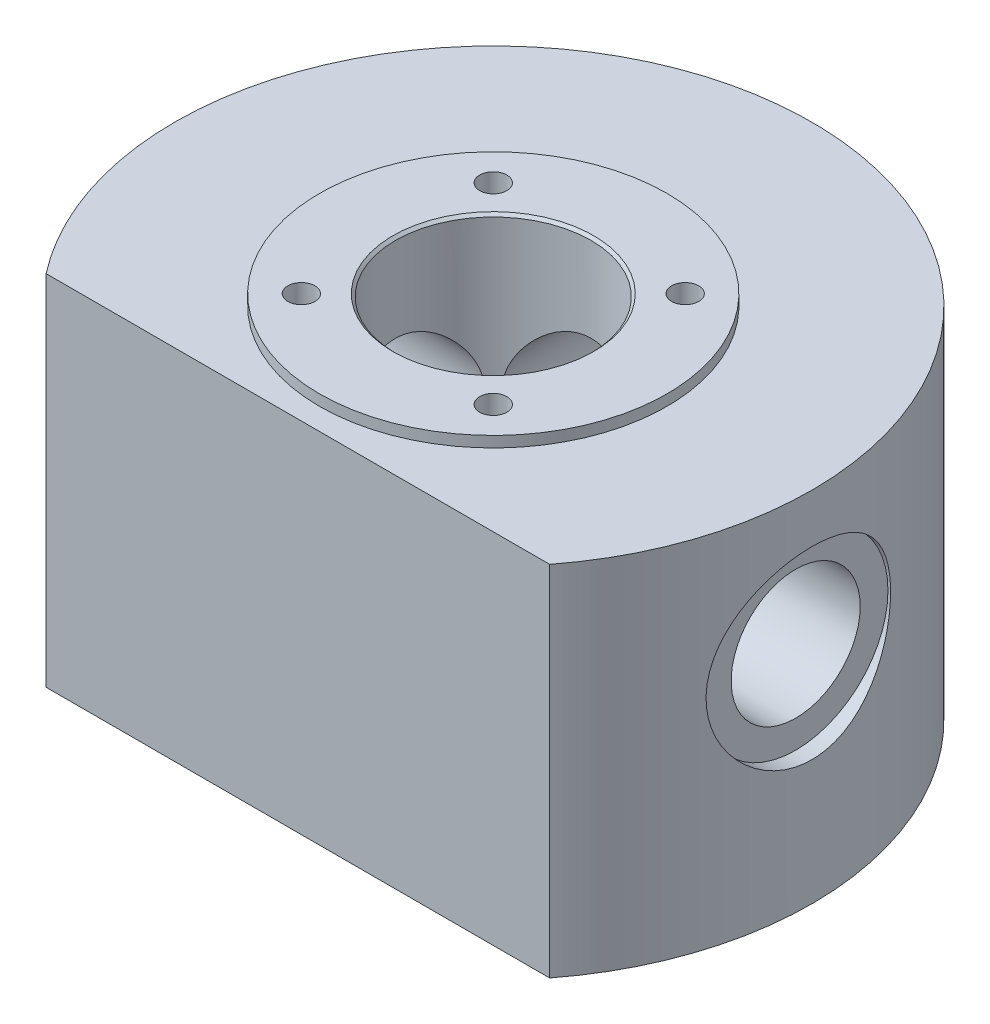
SolidWorks part; units mm, degrees
material "Chrome Stainless Steel"
ref_plane "Plano frontal" through (0, 0, 0) normal (0, 0, 1) x (1, 0, 0)
ref_plane "Plano superior" through (0, 0, 0) normal (0, 1, 0) x (1, 0, 0)
ref_plane "Plano direito" through (0, 0, 0) normal (1, 0, 0) x (0, 0, -1)
sketch "Esboço1" plane through (0, 0, 0) normal (0, 0, 1) x (1, 0, 0)
  line L0 (0, -20) -> (0, 0) construction
  line L1 (0, 0) -> (9, 0) construction
  line L2 (0, -20) -> (29.356, -20)
  line L3 (29.356, 13) -> (29.356, -20)
  line L4 (29.356, 13) -> (9, 13)
  line L5 (9, 13) -> (9, -13)
  line L6 (9, -13) -> (3, -13)
  line L7 (3, -13) -> (3, -17.6)
  line L8 (0, -20) -> (43.826, -20) construction
  line L9 (3, -17.6) -> (0, -17.6)
  line L10 (0, -17.6) -> (0, -20)
  dimension "D1" = 7
  dimension "D2" = 18
  dimension "D3" = 6
  dimension "D4" = 33
  dimension "D5" = 58.712
  dimension "D6" = 4.6
revolve "Revolução1" add sketch "Esboço1" angle 360 about L0
hole_wizard "Furo roscado de 1/4-18 NPSM1" positions "3DSketch2" profile "Esboço4" tap size "1/4-18 NPSM" standard "Ansi Inch" end condition up to next
sketch3d "3DSketch2"
  point P0 (0, 0, 0)
  point P4 (0, 0, 0)
  point P6 (29.356, 0, 0)
sketch "Esboço4" plane through (29.356, 0, 0) normal (0, 1, 0) x (0, 0, -1)
  line L0 (0, 0) -> (0, 29.356)
  line L1 (0, 29.356) -> (5.9436, 29.356)
  line L2 (5.9436, 29.356) -> (5.9436, 0)
  line L5 (5.9436, 0) -> (0, 0)
  line L11 (0, -6.35) -> (0, 107.95) construction
  dimension "Thru Tap Drill Dia." = 11.8872
  dimension "Thru Tap Drill Depth" = 29.356
cosmetic thread "Rosca de furo1" parameters "D2"=13.3604
ref_plane "Plano1" through (0, 0, -29.356) normal (0, 0, 1) x (0, -1, 0)
hole_wizard "Furo roscado de 1/4-18 NPSM3" positions "Esboço6" profile "Esboço5" tap size "1/4-18 NPSM" standard "Ansi Inch" end condition up to next
sketch "Esboço6" plane through (0, 0, -29.356) normal (0, 0, 1) x (0, -1, 0)
  point P0 (0, 0)
sketch "Esboço5" plane through (0, 0, -29.356) normal (1, 0, 0) x (0, 1, 0)
  line L0 (0, 0) -> (0, 20.356)
  line L1 (0, 20.356) -> (5.9436, 20.356)
  line L2 (5.9436, 20.356) -> (5.9436, 0)
  line L5 (5.9436, 0) -> (0, 0)
  line L11 (0, -6.35) -> (0, 107.95) construction
  dimension "Thread Major Dia." = 11.8872
  dimension "Thru Tap Drill Depth" = 20.356
ref_plane "Plano2" through (-29.356, 0, 0) normal (-1, 0, 0) x (0, -1, 0)
sketch "Esboço7" plane through (-29.356, 0, 0) normal (-1, 0, 0) x (0, -1, 0)
  circle A0 centre (0, 0) radius 3
  dimension "D1" = 6
extrude "Corte-extrusão1" [suppressed] cut sketch "Esboço7" against normal blind 6
ref_axis "Eixo1" through (0, 15.7, 0) along (0, -1, 0)
pattern_circular "PadrãoCircular1" [suppressed] count 2 every 17 about axis through (0, 15.7, 0) along (0, -1, 0) of bodies 131
pattern_circular "PadrãoCircular2" [suppressed] count 2 over 360 about axis through (0, 15.7, 0) along (0, -1, 0) of bodies 132
sketch "Esboço8" [suppressed] plane through (-16, 0, 0) normal (-1, 0, 0) x (0, -1, 0)
  line L0 (9.5, -16) -> (9.5, 16) construction
  line L1 (-6, -4) -> (9.5, -4)
  line L2 (-6, -4) -> (-6, 4)
  line L3 (-6, 4) -> (9.5, 4)
  line L4 (9.5, -4) -> (9.5, 4)
  circle A1 centre (0, 0) radius 3 construction
  dimension "D2" = 4
  dimension "D3" = 4
  dimension "D1" = 6
extrude "Corte-extrusão2" [suppressed] cut sketch "Esboço8" against normal blind 2
pattern_circular "PadrãoCircular3" [suppressed] count 2 every 17 about axis through (0, 15.7, 0) along (0, -1, 0) of bodies 134
pattern_circular "PadrãoCircular4" [suppressed] count 2 over 360 about axis through (0, 15.7, 0) along (0, -1, 0) of bodies 135
ref_plane "Plano3" through (0, -20, 0) normal (0, -1, 0) x (-1, 0, 0)
sketch "Esboço9" [suppressed] plane through (0, -9.5, 0) normal (0, -1, 0) x (-1, 0, 0)
  line L0 (14, -7.746) -> (14, 2.0923)
  line L1 (14, 2.0923) -> (11.1236, 11.5007)
  line L2 (12.2188, 7.9184) -> (14, 2.0923) construction
  line L3 (14, -4) -> (14, 2.0923) construction
  line L6 (-14, -7.746) -> (-14, 7.746)
  line L8 (-14, 4) -> (-14, -4) construction
  arc A0 (14, -7.746) -> (11.1236, 11.5007) centre (0, 0) ccw
  arc A1 (-14, 7.746) -> (-14, -7.746) centre (0, 0) ccw
extrude "Corte-extrusão3" [suppressed] cut sketch "Esboço9" against normal through all
ref_plane "Plano4" through (0, 13, 0) normal (0, 1, 0) x (1, 0, 0)
sketch "Esboço12" plane through (0, 13, 0) normal (0, 1, 0) x (1, 0, 0)
  circle A0 centre (0, 0) radius 9
  circle A1 centre (0, 0) radius 16
  dimension "D1" = 18
  dimension "D2" = 32
extrude "Ressalto-extrusão1" add sketch "Esboço12" along normal blind 1
hole_wizard "Furo roscado de M3x0.51" positions "Esboço14" profile "Esboço13" tap size "M3x0.5" standard "Ansi Metric"
sketch "Esboço14" plane through (0, 14, 0) normal (0, 1, 0) x (1, 0, 0)
  line L0 (0, 16) -> (0, 0) construction
  line L1 (0, 0) -> (11.3137, 11.3137) construction
  circle A0 centre (0, 0) radius 12.5
  circle A1 centre (0, 0) radius 16 construction
  point P0 (8.8388, 8.8388)
  dimension "D2" = 25
  dimension "D1" = 45
sketch "Esboço13" plane through (8.8388, 14, -8.8388) normal (1, 0, 0) x (0, 0, 1)
  line L0 (0, 0) -> (0, 10.7511)
  line L1 (0, 10.7511) -> (1.25, 10)
  line L2 (1.25, 10) -> (1.25, 0)
  line L5 (1.25, 0) -> (0, 0)
  line L10 (0, 10.7511) -> (-1.25, 10) construction
  line L11 (0, -6.35) -> (0, 107.95) construction
  dimension "Tap Drill Dia." = 2.5
  dimension "Tap Drill Depth" = 10
  dimension "Drill Angle" = 118
ref_axis "Eixo2" through (0, -21.7, 0) along (0, 1, 0)
pattern_circular "PadrãoCircular5" count 4 over 360 about axis through (0, -21.7, 0) along (0, 1, 0) of "Furo roscado de M3x0.51"
chamfer "Chanfro1" distance 0.5 angle 45 1 edges at (0, -13, -3)
chamfer "Chanfro2" distance 0.25 angle 45 1 edges at (0, 14, 9)
hole_wizard "Furo roscado de 1/4-18 NPSM2" positions "3DSketch4" profile "Esboço17" tap size "1/4-18 NPSM" standard "Ansi Inch" end condition up to next
sketch3d "3DSketch4"
  line L0 (0, 0, 0) -> (0, 0, 1.819) construction
  line L4 (0, 0, 0) -> (-29.356, 0, 0)
  point P0 (-29.356, 0, 0)
sketch "Esboço17" plane through (-29.356, 0, 0) normal (0, 1, 0) x (0, 0, 1)
  line L0 (0, 0) -> (0, 20.356)
  line L1 (0, 20.356) -> (5.9436, 20.356)
  line L2 (5.9436, 20.356) -> (5.9436, 0)
  line L5 (5.9436, 0) -> (0, 0)
  line L11 (0, -6.35) -> (0, 107.95) construction
  dimension "Thread Major Dia." = 11.8872
  dimension "Thru Tap Drill Depth" = 20.356
sketch "Esboço18" plane through (-29.356, 0, 0) normal (-1, 0, 0) x (0, -1, 0)
  circle A0 centre (0, 0) radius 8.5
  dimension "D1" = 17
extrude "Corte-extrusão4" cut sketch "Esboço18" against normal blind 1.5
sketch "Esboço20" plane through (0, 0, -29.356) normal (0, 0, 1) x (0, -1, 0)
  circle A0 centre (0, 0) radius 8.5
  dimension "D1" = 17
extrude "Corte-extrusão5" cut sketch "Esboço20" along normal blind 1.5
mirror "Espelhar1" about plane through (0, 0, 0) normal (1, 0, 0) of "Corte-extrusão4"
sketch "Esboço21" plane through (0, 13, 0) normal (0, 1, 0) x (1, 0, 0)
  line L0 (-23.19, -18) -> (23.19, -18)
  circle A0 centre (0, 0) radius 29.356 construction
  arc A1 (-23.19, -18) -> (23.19, -18) centre (0, 0) ccw
  dimension "D1" = 18
extrude "Corte-extrusão6" cut sketch "Esboço21" against normal through all
equation "\"D1@Esboço20\"=\"D1@Esboço18\""
